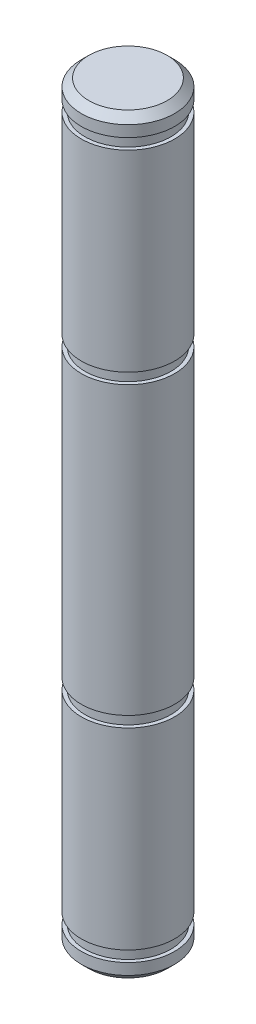
SolidWorks part; units mm, degrees
ref_plane "Front" through (0, 0, 0) normal (0, 0, 1) x (1, 0, 0)
ref_plane "Top" through (0, 0, 0) normal (0, 1, 0) x (1, 0, 0)
ref_plane "Right" through (0, 0, 0) normal (1, 0, 0) x (0, 0, -1)
ref_axis "side-side" through (80.9, 0, 0) along (-1, 0, 0)
ref_axis "up-down" through (0, 50, 0) along (0, -1, 0)
ref_axis "front-back" through (0, 0, -80.9) along (0, 0, 1)
sketch "Sketch1" plane through (0, 0, 0) normal (0, 0, 1) x (1, 0, 0)
  line L0 (-3.175, 23.5585) -> (-3.175, 10.4775)
  line L1 (0, 25.5651) -> (-3.175, 25.5651)
  line L2 (0, 25.5651) -> (0, -25.5651)
  line L3 (0, -25.5651) -> (-3.175, -25.5651)
  line L4 (-3.175, 25.5651) -> (-3.175, 24.2951)
  line L5 (-3.175, 24.2951) -> (-2.921, 24.2951)
  line L6 (-3.175, -24.2951) -> (-3.175, -25.5651)
  line L7 (-3.175, 23.5585) -> (-2.921, 23.5585)
  line L8 (-2.921, 24.2951) -> (-2.921, 23.5585)
  line L9 (-3.175, -23.5585) -> (-2.921, -23.5585)
  line L10 (0, 25.5651) -> (0, 13.3378) construction
  line L11 (-3.175, -24.2951) -> (-2.921, -24.2951)
  line L12 (-2.921, -23.5585) -> (-2.921, -24.2951)
  line L13 (3.175, 22.7965) -> (-3.175, 22.7965) construction
  line L14 (-6.35, 11.1125) -> (6.35, 11.1125) construction
  line L15 (-3.175, 10.4775) -> (-2.921, 10.4775)
  line L16 (-3.175, 9.7409) -> (-3.175, -9.7409)
  line L17 (-3.175, 9.7409) -> (-2.921, 9.7409)
  line L18 (-2.921, 10.4775) -> (-2.921, 9.7409)
  line L19 (-3.175, -9.7409) -> (-2.921, -9.7409)
  line L21 (-3.175, -10.4775) -> (-2.921, -10.4775)
  line L22 (-2.921, -9.7409) -> (-2.921, -10.4775)
  line L23 (-3.175, -10.4775) -> (-3.175, -23.5585)
  dimension "D1" = 6.35
  dimension "D2" = 0.7366
  dimension "D3" = 1.27
  dimension "D4" = 47.117
  dimension "D5" = 0.254
  dimension "D6" = 0.762
  dimension "D7" = 0.635
revolve "Revolve1" add sketch "Sketch1" angle 360 about L10
chamfer "Chamfer1" distance 0.508 angle 45 2 edges at (-3.175, -25.5651, 0) (-3.175, 25.5651, 0)
